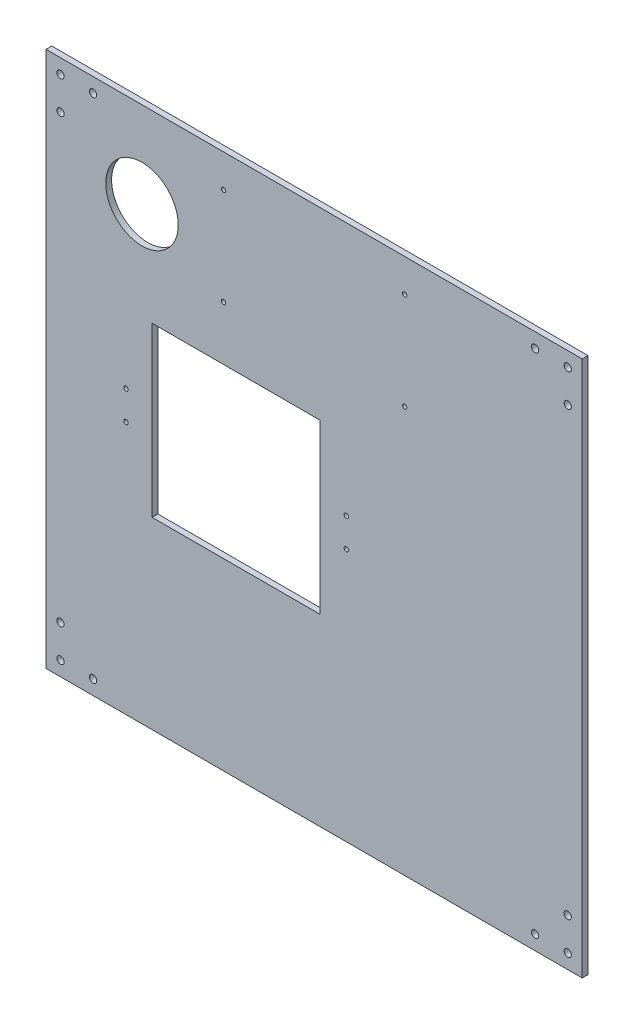
SolidWorks part; units mm, degrees
ref_plane "前视基准面" through (0, 0, 0) normal (0, 0, 1) x (1, 0, 0)
ref_plane "上视基准面" through (0, 0, 0) normal (0, 1, 0) x (1, 0, 0)
ref_plane "右视基准面" through (0, 0, 0) normal (1, 0, 0) x (0, 0, -1)
sketch "草图1" plane through (0, 0, 0) normal (0, 0, 1) x (1, 0, 0)
  line L1 (185, -185) -> (-185, -185)
  line L2 (185, -185) -> (185, 185)
  line L3 (185, 185) -> (-185, 185)
  line L4 (-185, -185) -> (-185, 185)
  line L5 (185, -185) -> (-185, 185) construction
  line L6 (185, 185) -> (-185, -185) construction
  point P0 (0, 0)
  dimension "D1" = 370
  dimension "D2" = 370
extrude "凸台-拉伸1" add sketch "草图1" along normal blind 4
sketch "草图2" plane through (0, 0, 4) normal (0, 0, 1) x (1, 0, 0)
  line L0 (-165, -175) -> (-152.5, -175) construction
  line L1 (-185, -185) -> (-165, -185) construction
  line L2 (-185, -185) -> (-185, -165) construction
  line L3 (-185, -165) -> (-165, -165) construction
  line L4 (-165, -185) -> (-165, -165) construction
  line L5 (-175, -165) -> (-175, -152.5) construction
  circle A0 centre (-175, -175) radius 2.5
  circle A1 centre (-152.5, -175) radius 2.5
  circle A2 centre (-175, -152.5) radius 2.5
  circle A3 centre (-152.5, 175) radius 2.5
  circle A4 centre (-175, 152.5) radius 2.5
  circle A5 centre (-175, 175) radius 2.5
  circle A6 centre (175, 152.5) radius 2.5
  circle A7 centre (152.5, 175) radius 2.5
  circle A8 centre (175, 175) radius 2.5
  circle A9 centre (152.5, -175) radius 2.5
  circle A10 centre (175, -152.5) radius 2.5
  circle A11 centre (175, -175) radius 2.5
  point P34 (0, 0)
  dimension "D3" = 10
  dimension "D4" = 10
  dimension "D5" = 5
  dimension "D6" = 12.5
  dimension "D7" = 5
  dimension "D9" = 5
  dimension "D1" = 20
  dimension "D2" = 20
  dimension "D8" = 12.5
  dimension "D10" = 4
extrude "切除-拉伸1" cut sketch "草图2" against normal through all
sketch "草图4" plane through (0, 0, 0) normal (0, 0, -1) x (-1, 0, 0)
  line L0 (-4.2271, -58.09) -> (111.7729, -58.09)
  line L1 (111.7729, -58.09) -> (111.7729, 57.91)
  line L2 (111.7729, 57.91) -> (-4.2271, 57.91)
  line L3 (-4.2271, 57.91) -> (-4.2271, -58.09)
extrude "切除-拉伸5" cut sketch "草图4" against normal through all
sketch "草图5" plane through (0, 0, 0) normal (0, 0, -1) x (-1, 0, 0)
  circle A0 centre (-22.2271, -10.09) radius 1.5
  circle A1 centre (-22.2271, 9.91) radius 1.5
  circle A2 centre (129.7729, 9.91) radius 1.5
  circle A3 centre (129.7729, -10.09) radius 1.5
extrude "切除-拉伸6" cut sketch "草图5" against normal through all
sketch "草图6" plane through (0, 0, 0) normal (0, 0, -1) x (-1, 0, 0)
  line L1 (62.5, 95.2498) -> (-62.5, 95.2498) construction
  line L2 (62.5, 95.2498) -> (62.5, 162.2498) construction
  line L3 (62.5, 162.2498) -> (-62.5, 162.2498) construction
  line L4 (-62.5, 95.2498) -> (-62.5, 162.2498) construction
  line L5 (62.5, 95.2498) -> (-62.5, 162.2498) construction
  line L6 (62.5, 162.2498) -> (-62.5, 95.2498) construction
  circle A0 centre (-62.5, 162.2498) radius 1.5
  circle A1 centre (-62.5, 95.2498) radius 1.5
  circle A2 centre (62.5, 95.2498) radius 1.5
  circle A3 centre (62.5, 162.2498) radius 1.5
  point P0 (0, 128.7498)
  dimension "D3" = 3
  dimension "D4" = 3
  dimension "D5" = 3
  dimension "D6" = 3
  dimension "D1" = 67
  dimension "D2" = 125
extrude "切除-拉伸7" cut sketch "草图6" against normal through all
sketch "草图7" plane through (0, 0, 0) normal (0, 0, -1) x (-1, 0, 0)
  circle A0 centre (118.7699, 125.6318) radius 25
  dimension "D1" = 50
extrude "切除-拉伸8" cut sketch "草图7" against normal through all
